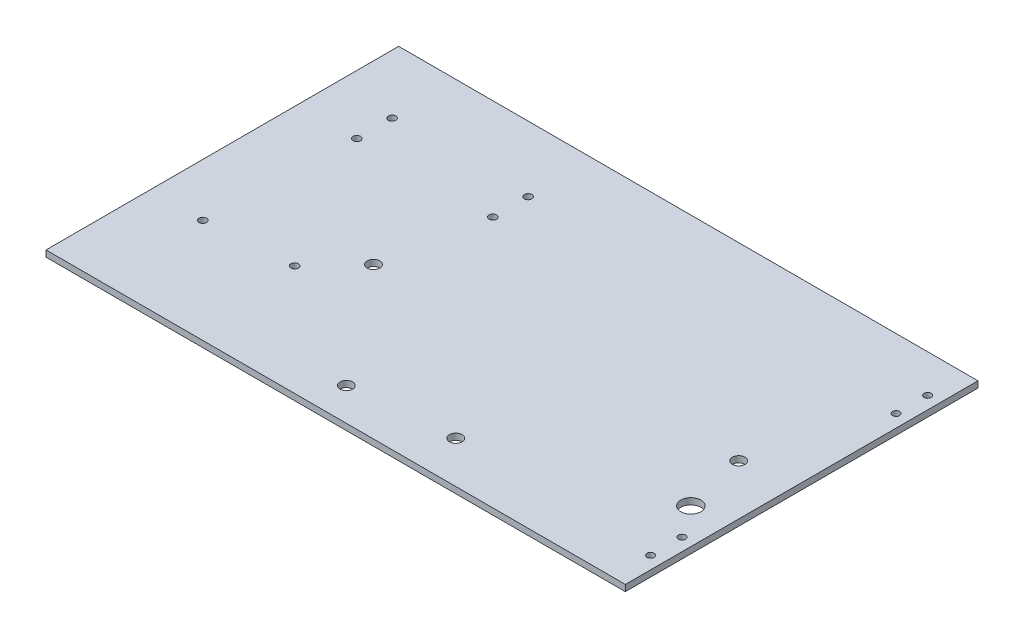
SolidWorks part; units mm, degrees
ref_plane "Front Plane" through (0, 0, 0) normal (0, 0, 1) x (1, 0, 0)
ref_plane "Top Plane" through (0, 0, 0) normal (0, 1, 0) x (1, 0, 0)
ref_plane "Right Plane" through (0, 0, 0) normal (1, 0, 0) x (0, 0, -1)
sketch "Sketch1" plane through (0, 0, 0) normal (0, 1, 0) x (1, 0, 0)
  line L1 (-158.75, 88.9) -> (158.75, 88.9)
  line L2 (-158.75, 88.9) -> (-158.75, -88.9)
  line L3 (-158.75, -88.9) -> (158.75, -88.9)
  line L4 (158.75, 88.9) -> (158.75, -88.9)
  line L5 (-158.75, 88.9) -> (158.75, -88.9) construction
  line L6 (-158.75, -88.9) -> (158.75, 88.9) construction
  circle A0 centre (-69.85, -12.7) radius 3.175
  circle A1 centre (107.95, -6.35) radius 3.175
  circle A4 centre (-129.032, 55.88) radius 1.905
  circle A5 centre (-60.452, 55.88) radius 1.905
  circle A7 centre (-129.032, 38.1) radius 1.905
  circle A8 centre (-60.452, 38.1) radius 1.905
  point P0 (0, 0)
  dimension "D3" = 6.35
  dimension "D4" = 6.35
  dimension "D14" = 3.81
  dimension "D17" = 17.78
  dimension "D1" = 317.5
  dimension "D2" = 177.8
  dimension "D5" = 88.9
  dimension "D6" = 266.7
  dimension "D7" = 95.25
  dimension "D8" = 76.2
  dimension "D13" = 29.718
  dimension "D15" = 68.58
  dimension "D16" = 127
extrude "Boss-Extrude1" add sketch "Sketch1" along normal blind 3.175
sketch "Sketch2" plane through (0, 3.175, 0) normal (0, 1, 0) x (1, 0, 0)
  line L0 (-158.75, 88.9) -> (-158.75, -88.9) construction
  line L1 (-158.75, -88.9) -> (158.75, -88.9) construction
  circle A0 centre (-89.0817, -33.177) radius 1.905
  circle A1 centre (-132.1376, -36.4483) radius 1.905
  dimension "D1" = 3.81
  dimension "D2" = 69.6683
  dimension "D3" = 52.4517
  dimension "D4" = 55.723
  dimension "D5" = 43.18
extrude "Cut-Extrude1" cut sketch "Sketch2" against normal through all
sketch "Sketch3" plane through (0, 0, 0) normal (0, -1, 0) x (-1, 0, 0)
  line L0 (158.75, -88.9) -> (-158.75, -88.9) construction
  line L1 (158.75, 88.9) -> (158.75, -88.9) construction
  circle A0 centre (23.8295, -72.39) radius 3.175
  circle A1 centre (-26.7643, -67.818) radius 3.175
  dimension "D1" = 6.35
  dimension "D2" = 4.572
  dimension "D3" = 16.51
  dimension "D4" = 185.5143
  dimension "D5" = 50.8
extrude "Cut-Extrude2" cut sketch "Sketch3" against normal through all
sketch "Sketch4" plane through (0, 3.175, 0) normal (0, 1, 0) x (1, 0, 0)
  line L0 (-158.75, -88.9) -> (158.75, -88.9) construction
  line L1 (158.75, 88.9) -> (133.35, 88.9)
  line L2 (158.75, 88.9) -> (158.75, -88.9)
  line L3 (158.75, -88.9) -> (133.35, -88.9)
  line L4 (133.35, 88.9) -> (133.35, -88.9)
  dimension "D1" = 25.4
extrude "Cut-Extrude3" cut sketch "Sketch4" against normal through all
sketch "Sketch5" plane through (0, 3.175, 0) normal (0, 1, 0) x (1, 0, 0)
  line L0 (133.35, 88.9) -> (-158.75, 88.9) construction
  line L1 (133.35, 88.9) -> (133.35, -88.9) construction
  circle A0 centre (115.57, -38.1) radius 5.08
  dimension "D3" = 10.16
  dimension "D1" = 127
  dimension "D2" = 17.78
extrude "Cut-Extrude4" cut sketch "Sketch5" against normal through all
sketch "Sketch6" plane through (0, 0, 0) normal (0, -1, 0) x (1, 0, 0)
  line L0 (-158.75, 88.9) -> (133.35, 88.9) construction
  line L1 (133.35, -88.9) -> (133.35, 88.9) construction
  line L2 (133.35, -88.9) -> (-158.75, -88.9) construction
  circle A0 centre (127, 69.85) radius 1.8034
  circle A2 centre (127, 53.975) radius 1.8034
  circle A3 centre (127, -53.975) radius 1.8034
  circle A4 centre (127, -69.85) radius 1.8034
  dimension "D4" = 3.6068
  dimension "D5" = 6.35
  dimension "D1" = 15.875
  dimension "D2" = 19.05
  dimension "D3" = 6.35
  dimension "D6" = 15.875
  dimension "D7" = 19.05
extrude "Cut-Extrude5" cut sketch "Sketch6" against normal through all
